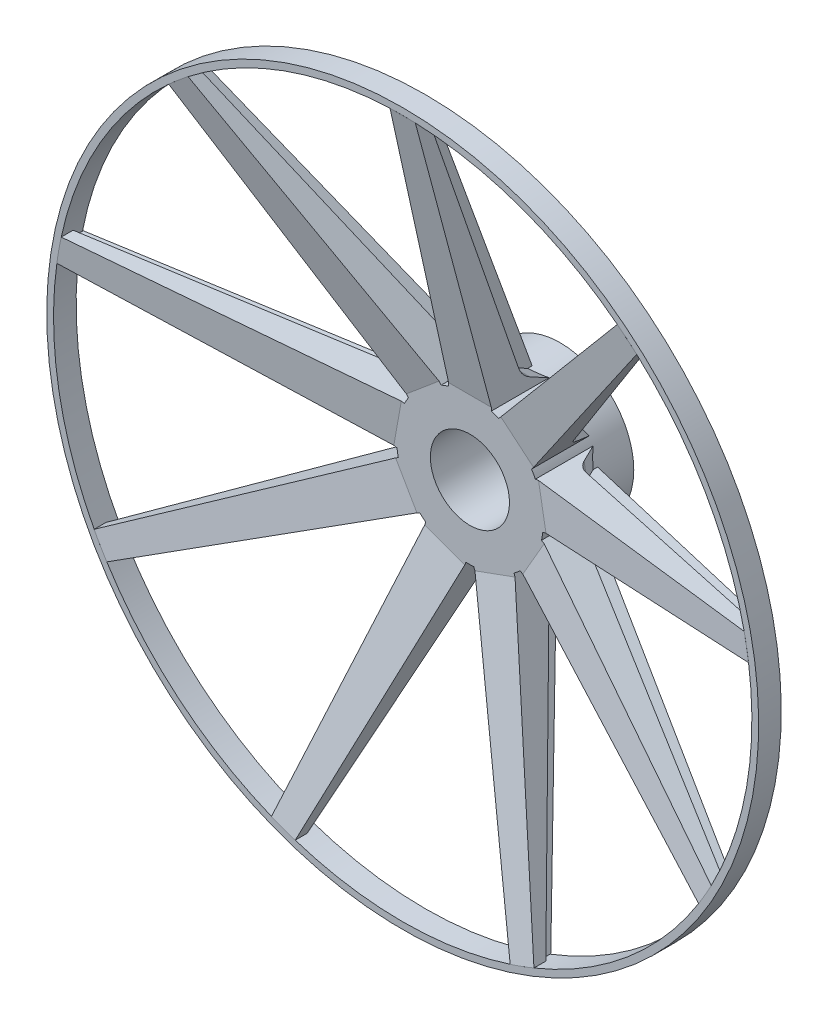
SolidWorks part; units mm, degrees
ref_plane "Front Plane" through (0, 0, 0) normal (0, 0, 1) x (1, 0, 0)
ref_plane "Top Plane" through (0, 0, 0) normal (0, 1, 0) x (1, 0, 0)
ref_plane "Right Plane" through (0, 0, 0) normal (1, 0, 0) x (0, 0, -1)
sketch "Sketch1" plane through (0, 0, 0) normal (0, 0, 1) x (1, 0, 0)
  line L0 (-20.031, 0) -> (20.031, 0) construction
  line L1 (0, 20.031) -> (0, -20.031) construction
  circle A1 centre (0, 0) radius 17.5
  circle A2 centre (0, 0) radius 32.5
  dimension "D1" = 35
  dimension "D2" = 65
extrude "Boss-Extrude1" add sketch "Sketch1" along normal blind 40
sketch "Sketch2" plane through (0, 0, 0) normal (0, 0, -1) x (-1, 0, 0)
  point P0 (0, 0)
sketch "Sketch3" plane through (0, 0, 0) normal (0, 1, 0) x (1, 0, 0)
  line L0 (0, 8.7146) -> (0, -51.2596) construction
sketch "Sketch4" plane through (0, 0, 0) normal (1, 0, 0) x (0, 0, -1)
  line L0 (-40, 32.5) -> (-15, 32.5)
  line L3 (-70.4963, 157.5) -> (-40, 32.5)
  line L4 (8.7146, 0) -> (-51.2596, 0) construction
  line L6 (-60.4963, 157.5) -> (-70.4963, 157.5)
  line L7 (-15, 32.5) -> (-60.4963, 157.5)
  dimension "D1" = 157.5
  dimension "D2" = 70
sketch "Sketch5" plane through (0, 0, 0) normal (0, 0, -1) x (-1, 0, 0)
extrude "Boss-Extrude2" add sketch "Sketch4" along normal blind 9.5 and the other way blind 9.5
sketch "Sketch6" plane through (0, 0, 40) normal (0, 0, 1) x (1, 0, 0)
  line L0 (-9.5, 32.5) -> (-9.5, 30.5512)
  line L1 (-9.5, 30.5512) -> (9.5, 30.5512)
  line L2 (9.5, 30.5512) -> (9.5, 32.5)
  line L3 (-9.5, 32.5) -> (9.5, 32.5)
  circle A0 centre (0, 0) radius 32.5
  circle M1 centre (0, 0) radius 32.5
extrude "Boss-Extrude3" add sketch "Sketch6" against normal blind 25 contours L3 L0 M1 | L3 L2 M1 | L1 L2 L0 M1 region at (-7.1355, 32.0758, 40) region at (0, 31.3512, 40) region at (7.1355, 32.0758, 40)
sketch "Sketch7" plane through (9.5, 0, 0) normal (1, 0, 0) x (0, 0, -1)
  line L0 (-15, 32.5) -> (-15.675, 34.3545)
  line L1 (-15, 32.5) -> (-60.4963, 157.5) construction
  line L2 (-15.675, 34.3545) -> (-14.4834, 31.0805)
  line L3 (-15, 31.0805) -> (-14.4834, 31.0805)
  line M2 (-15, 31.0805) -> (-15, 32.5)
extrude "Boss-Extrude4" add sketch "Sketch7" against normal blind 19 contours L3 L2 M2 region at (9.5, 31.5537, 14.8278)
sketch "Sketch10" plane through (-9.5, 0, 0) normal (-1, 0, 0) x (0, 0, 1)
  line L0 (65.4963, 157.5) -> (27.6827, 41.3021)
  line L1 (60.4963, 157.5) -> (70.4963, 157.5) construction
  line L3 (14.4834, 31.0805) -> (22.8914, 35.5794)
  line L4 (14.4834, 31.0805) -> (60.4963, 157.5)
  line L5 (60.4963, 157.5) -> (65.4963, 157.5)
  arc A0 (27.6827, 41.3021) -> (22.8914, 35.5794) centre (18.1735, 44.3966) cw
  point P5 (26.438, 37.4771)
  point P6 (26.438, 37.4771)
  dimension "D1" = 10
sketch "Sketch16" plane through (-9.5, 0, 0) normal (-1, 0, 0) x (0, 0, 1)
  line L5 (14.4834, 31.0805) -> (35.81, 31.0805) construction
  line L6 (40, 31.0805) -> (14.4834, 31.0805) construction
  line L7 (27.2417, 31.0805) -> (26.4088, 28.3283)
extrude "Cut-Extrude3" cut sketch "Sketch10" against normal blind 7
mirror "Mirror1" about plane through (0, 0, 0) normal (1, 0, 0) of "Cut-Extrude3"
sketch "Sketch18" plane through (0, -4.1909, 12.8782) normal (0, 0.3095, -0.9509) x (-1, 0, 0)
  line L0 (-2.5, 170.0371) -> (-5.5, 170.0371)
  line L2 (2.5, 170.0371) -> (5.5, 170.0371)
  line L3 (2.5, 170.0371) -> (9.5, 170.0371) construction
  line L4 (-2.5, 170.0371) -> (-9.5, 170.0371) construction
sketch3d "3DSketch1" plane through (0, 0, 0) normal (0, 0, 1) x (1, 0, 0)
sketch "Sketch20" plane through (0, 0, 0) normal (0, 0, -1) x (-1, 0, 0)
  line L0 (5.5, 157.5) -> (9.5, 29.7044)
  line L1 (9.5, 31.0805) -> (9.5, 28.3283) construction
  line L2 (9.5, 29.7044) -> (9.5, 157.5)
  line L3 (9.5, 157.5) -> (5.5, 157.5)
  line L4 (-5.5, 157.5) -> (-9.5, 31.0805)
  line L5 (-9.5, 31.0805) -> (-9.5, 157.5)
  line L6 (-9.5, 157.5) -> (-5.5, 157.5)
extrude "Cut-Extrude6" cut sketch "Sketch20" against normal through all
pattern_circular "CirPattern11" count 9 over 360 about axis through (0, 0, 0) along (0, 0, 1) of bodies 112
sketch "Sketch22" plane through (0, 0, 0) normal (0, 0, -1) x (-1, 0, 0)
  circle A0 centre (0, 0) radius 158.5
  circle A1 centre (0, 0) radius 154.5
  dimension "D1" = 317
extrude "Cut-Extrude8" cut sketch "Sketch22" against normal through all
ref_plane "Plane1" through (0, 0, 69.7396) normal (0, 0, -1) x (-1, 0, 0)
sketch "Sketch23" plane through (0, 0, 69.7396) normal (0, 0, -1) x (-1, 0, 0)
  circle A0 centre (0, 0) radius 157.5
  circle A1 centre (0, 0) radius 154.5
  dimension "D1" = 315
  dimension "D2" = 309
extrude "Boss-Extrude5" add sketch "Sketch23" along normal blind 10
